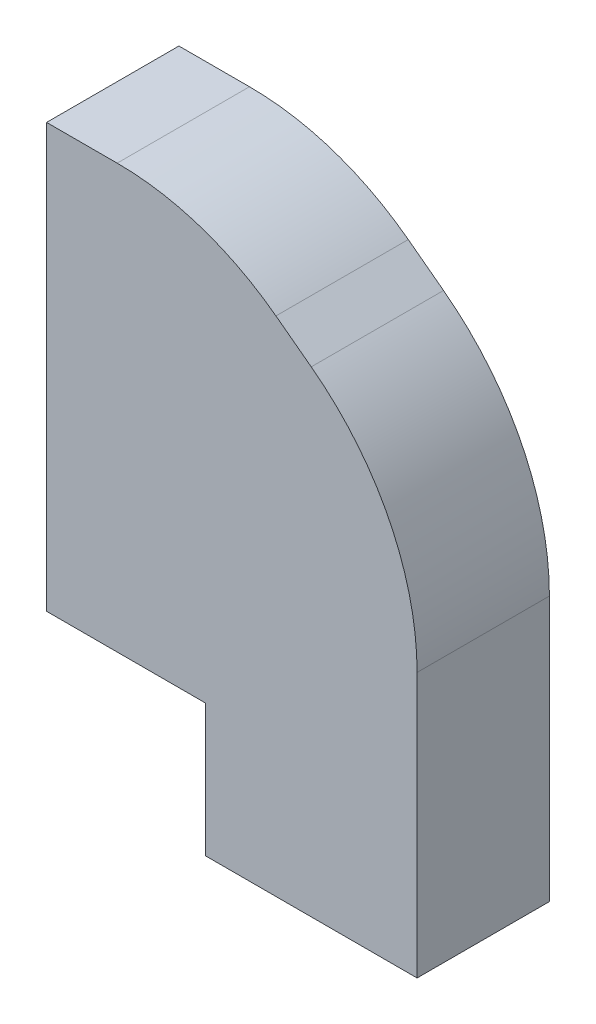
SolidWorks part; units mm, degrees
material "PBT General Purpose"
ref_plane "Front Plane" through (0, 0, 0) normal (0, 0, 1) x (1, 0, 0)
ref_plane "Top Plane" through (0, 0, 0) normal (0, 1, 0) x (1, 0, 0)
ref_plane "Right Plane" through (0, 0, 0) normal (1, 0, 0) x (0, 0, -1)
sketch "frame_outline" plane through (0, 0, 0) normal (0, 0, 1) x (1, 0, 0)
  line L0 (0, 0) -> (0.3, 0)
  line L1 (0.3, 0) -> (0.3, -0.25)
  line L2 (0.3, -0.25) -> (0.7, -0.25)
  line L3 (0.7, -0.25) -> (0.7, -0.1287)
  line L84 (0.7, -0.1287) -> (0.7, 0.5)
  line L87 (0, 0.8) -> (0, 0)
  line L88 (0, 0.8) -> (0.3, 0.8)
  line L89 (0.3, 0.8) -> (0.7, 0.5)
  dimension "D1" = 0.8
  dimension "D2" = 0.3
  dimension "D3" = 0.4
  dimension "D4" = 0.25
  dimension "D5" = 0.3
  dimension "D6" = 0.5
extrude "Boss-Extrude1" add sketch "frame_outline" along normal mid plane 0.25
fillet "Fillet1" radius 0.5 2 edges at (0.7, 0.5, 0) (0.3, 0.8, 0)
equation "\"t\"= 0.25'thickness of the sheets"
equation "\"t_cf\"= 0.115'thickness of single carbon fiber layer"
equation "\"t_kapton\"= 0.025'thickness of single Kapton flex layer"
equation "\"t_fr4\"= 0.1'thickness of FR4 with copper layer"
equation "\"joint_flex\"= 0.1'Width of flextures gap"
equation "\"joint_flex_eff\"= 0.02'Width of flecture after castelation"
equation "\"joint_fold\"= 0.2'Width of folding joints for 90deg fold"
equation "\"gap_tolerance\"= 0.002'Width to have interfecence fit between carbon fiber inserts"
equation "\"assemble_angle\"= 90'Angle of assembly parts"
equation "\"D1@Boss-Extrude1\"=\"t\""
equation "\"link_lift\"= 0.5'Actuation linkage amplification for the lift motion"
equation "\"link_swing\"= 0.45'Actuation linkage amplification for the swing motion"
equation "\"D4@frame_outline\"=\"t\""
